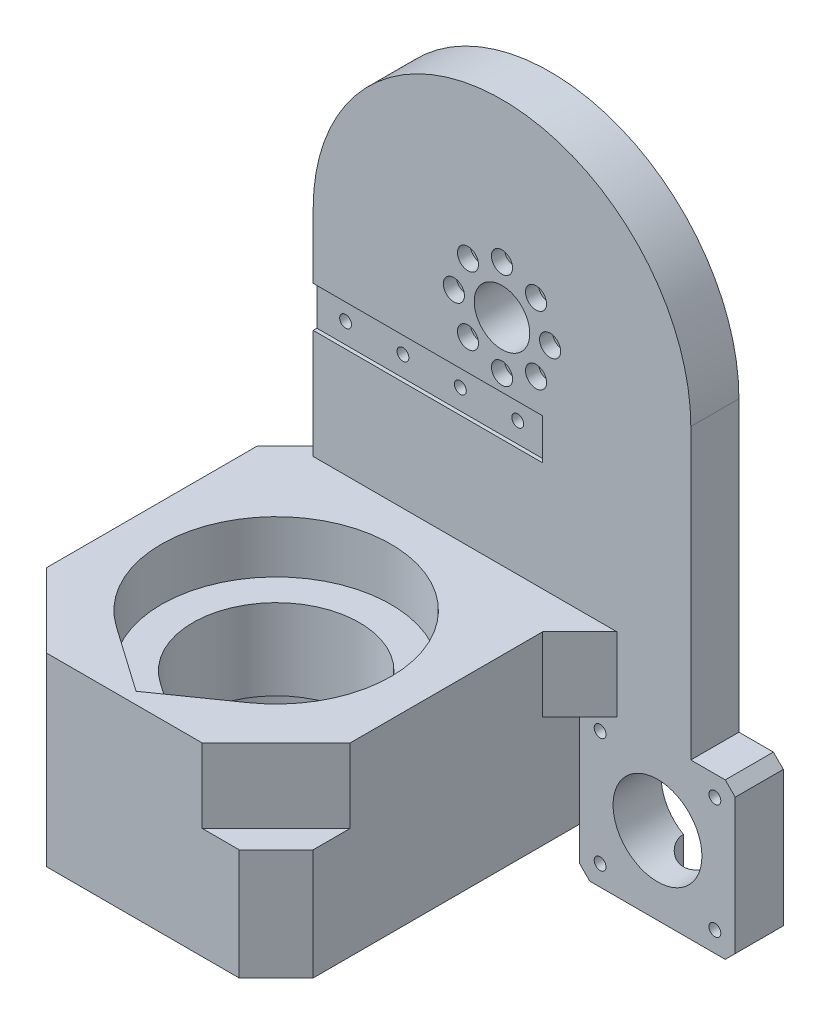
SolidWorks part; units mm, degrees
ref_plane "Front Plane" through (0, 0, 0) normal (1, 0, 0) x (0, 1, 0)
ref_plane "Top Plane" through (0, 0, 0) normal (0, 0, 1) x (0, 1, 0)
ref_plane "Right Plane" through (0, 0, 0) normal (0, 1, 0) x (-1, 0, 0)
sketch "Sketch1" plane through (0, 0, 0) normal (0, 0, 1) x (0, 1, 0)
  line L0 (0, 0) -> (-50000, 0) construction
  line L1 (22, 21) -> (67, 21) construction
  line L2 (22, 21) -> (22, -21) construction
  line L3 (22, -21) -> (67, -21) construction
  line L4 (67, 21) -> (67, -21) construction
  line L5 (-32, 31) -> (-18, 31)
  line L6 (-32, 31) -> (-32, -31)
  line L7 (-32, -31) -> (-18, -31)
  line L8 (-18, 31) -> (-18, -31)
  line L9 (-68, -31) -> (-54, -31)
  line L10 (-54, 31) -> (-54, -31)
  line L11 (-68, 31) -> (-54, 31)
  line L12 (-68, 31) -> (-68, -31)
  line L13 (-80, -43.6985) -> (-77.3015, -41)
  line L14 (-77.3015, -41) -> (-73, -41)
  line L15 (-80, -43.6985) -> (-80, -80.3015)
  line L16 (-77.3015, -83) -> (-40.6985, -83)
  line L17 (-38, -71) -> (-38, -80.3015)
  line L18 (0, 0) -> (0, -20) construction
  line L19 (0, -20) -> (40, -20) construction
  line L22 (40, 41) -> (-68, 41)
  line L24 (-80, -80.3015) -> (-77.3015, -83)
  line L25 (-73, -41) -> (-18, -41)
  line L26 (-18, -41) -> (-18, -31)
  line L27 (-18, 31) -> (-18, 41)
  line L28 (-68, -31) -> (-68, -41)
  line L29 (-68, 41) -> (-68, 31)
  line L30 (40, 41) -> (40, 31)
  line L31 (40, 31) -> (-18, 31)
  line L32 (40, -71) -> (-38, -71)
  line L33 (-40.6985, -83) -> (-38, -80.3015)
  line L34 (-54, 31) -> (-32, 31)
  line L36 (-43.5, -46.5) -> (-74.5, -46.5) construction
  line L37 (-43.5, -46.5) -> (-43.5, -77.5) construction
  line L38 (-43.5, -77.5) -> (-74.5, -77.5) construction
  line L39 (-74.5, -46.5) -> (-74.5, -77.5) construction
  line L40 (-43.5, -46.5) -> (-74.5, -77.5) construction
  line L41 (-43.5, -77.5) -> (-74.5, -46.5) construction
  circle A0 centre (-59, -62) radius 12
  circle A1 centre (40, -20) radius 17.5
  circle A2 centre (40, -20) radius 13 construction
  circle A3 centre (40, -7) radius 1.6
  circle A4 centre (40, -7) radius 2.85
  circle A12 centre (40, -20) radius 7.5
  circle A13 centre (49.1924, -10.8076) radius 2.85
  circle A14 centre (49.1924, -10.8076) radius 1.6
  circle A15 centre (53, -20) radius 2.85
  circle A16 centre (53, -20) radius 1.6
  circle A17 centre (49.1924, -29.1924) radius 2.85
  circle A18 centre (49.1924, -29.1924) radius 1.6
  circle A19 centre (40, -33) radius 2.85
  circle A20 centre (40, -33) radius 1.6
  circle A21 centre (30.8076, -29.1924) radius 2.85
  circle A22 centre (30.8076, -29.1924) radius 1.6
  circle A23 centre (27, -20) radius 2.85
  circle A24 centre (27, -20) radius 1.6
  circle A25 centre (30.8076, -10.8076) radius 2.85
  circle A26 centre (30.8076, -10.8076) radius 1.6
  arc A27 (40, -71) -> (40, 31) centre (40, -20) ccw
  circle A28 centre (-74.5, -46.5) radius 1.6
  circle A29 centre (-74.5, -46.5) radius 2.85
  circle A30 centre (-43.5, -46.5) radius 2.85
  circle A31 centre (-43.5, -46.5) radius 1.6
  circle A32 centre (-43.5, -77.5) radius 2.85
  circle A33 centre (-43.5, -77.5) radius 1.6
  circle A34 centre (-74.5, -77.5) radius 2.85
  circle A35 centre (-74.5, -77.5) radius 1.6
  point P12 (-18, 0)
  point P16 (-54, 0)
  point P17 (22, 0)
  point P18 (-80, -41)
  point P19 (-38, -83)
  point P20 (-80, -83)
  dimension "D13" = 24
  dimension "D14" = 35
  dimension "D15" = 26
  dimension "D16" = 3.2
  dimension "D17" = 5.7
  dimension "D22" = 15
  dimension "D29" = 3.2
  dimension "D30" = 5.7
  dimension "D1" = 42
  dimension "D2" = 45
  dimension "D3" = 22
  dimension "D4" = 14
  dimension "D5" = 62
  dimension "D6" = 40
  dimension "D7" = 62
  dimension "D8" = 14
  dimension "D9" = 22
  dimension "D10" = 31
  dimension "D11" = 60
  dimension "D12" = 10
  dimension "D19" = 20
  dimension "D20" = 10
  dimension "D21" = 40
  dimension "D23" = 59
  dimension "D24" = 31
  dimension "D28" = 21
  dimension "D31" = 2
  dimension "D18" = 8
extrude "Boss-Extrude2" add sketch "Sketch1" against normal blind 13 contours L3 L1 L2 | L34 L10 L9 L28 L25 L26 L7 L6 | L11 L12 L9 L10 | L8 L5 L6 L7 | L32 A27 L31 L8 L26 L25 L14 L13 L15 L24 L16 L33 L17 A0 A1 | A1 A25 A23 A21 A19 A17 A15 A13 A12 A4 | A25 A26 | A4 A3 | A13 A14 | A15 A16 | A17 A18 | A19 A20 | A21 A22 | A23 A24 | A34 A35 | A32 A33 | A30 A31 | A29 A28 region at (0, -25, 0) region at (9.6567, -43, 0) region at (26.6311, 17.6235, 0) region at (0, -61, 0) region at (20, 22.995, 0) region at (7, 37.2306, 0) region at (10.8076, 46.423, 0) region at (20, 50.2306, 0) region at (29.1924, 46.423, 0) region at (33, 37.2306, 0) region at (29.1924, 28.0382, 0) region at (20, 24.2306, 0) region at (10.8076, 28.0382, 0) region at (46.5, -77.2694, 0) region at (46.5, -46.2694, 0) region at (77.5, -46.2694, 0) region at (77.5, -77.2694, 0)
extrude "Boss-Extrude3" add sketch "Sketch1<6>" along normal blind 82 contours L5 L27 L22 L25 L26 L7 L6 L12 L11 L10 L9 | L8 L5 L6 L7 | L11 L12 L9 L10 | L11 L34 L5 L27 L22 L29 region at (-36, -43, 0) region at (0, -25, 0) region at (9.6567, -43, 0) region at (0, -61, 0)
sketch "Sketch1<6>" plane through (0, 0, 0) normal (0, 0, 1) x (0, 1, 0) same geometry as "Sketch1"
extrude "Cut-Extrude2" cut sketch "Sketch1<5>" against normal blind 3.5 contours A21 | A23 | A25 | A4 | A13 | A15 | A17 | A19
sketch "Sketch1<5>" plane through (0, 0, 0) normal (0, 0, 1) x (0, 1, 0) same geometry as "Sketch1"
sketch "Sketch2" plane through (0, -18, 0) normal (0, 1, 0) x (-1, 0, 0)
  line L0 (-41, 82) -> (41, 0) construction
  line L1 (0, 41) -> (0, 78.844) construction
  line L2 (-17.7809, 66.3937) -> (0, 78.844)
  line L3 (17.7809, 66.3937) -> (0, 78.844)
  line L4 (-12.9055, 59.4309) -> (0, 68.4674)
  line L5 (12.9055, 59.4309) -> (0, 68.4674)
  line L6 (31, 0) -> (41, 0) construction
  arc A0 (-17.7809, 66.3937) -> (17.7809, 66.3937) centre (0, 41) ccw
  arc A1 (-12.9055, 59.4309) -> (12.9055, 59.4309) centre (0, 41) ccw
  point P5 (41, 0)
  point P13 (41, 0)
  dimension "D1" = 62
  dimension "D3" = 45
  dimension "D2" = 55
  dimension "D4" = 55
extrude "Cut-Extrude3" cut sketch "Sketch2" against normal blind 14.1 contours A0 L3 L2
extrude "Cut-Extrude4" cut sketch "Sketch2<3>" along normal blind 14.1 from surface starting at face at (-3, -68, 19.7143)
sketch "Sketch2<3>" plane through (0, -18, 0) normal (0, 1, 0) x (-1, 0, 0) same geometry as "Sketch2"
extrude "Cut-Extrude5" cut sketch "Sketch2<4>" against normal through all and the other way through all contours L4 A1 L5 region at (0, -18, 41.6528)
sketch "Sketch2<4>" plane through (0, -18, 0) normal (0, 1, 0) x (-1, 0, 0) same geometry as "Sketch2"
sketch "Sketch3" plane through (0, 0, 0) normal (0, 0, 1) x (1, 0, 0)
  line L1 (21, 22) -> (21, 67) construction
  line L2 (-21, 67) -> (21, 67) construction
  line L3 (-21, 22) -> (-21, 67) construction
  line L4 (-31, -18) -> (-31, 40) construction
  line L5 (21, 22) -> (21, 67) construction
  line L6 (-21, 67) -> (21, 67) construction
  line L7 (-21, 22) -> (-21, 67) construction
  line L8 (-21, 22) -> (21, 22) construction
  line L9 (-21, 22) -> (21, 22) construction
  line L10 (0, 22) -> (0, 17) construction
  line L11 (31, 11.5) -> (-31, 11.5)
  line L12 (31, 11.5) -> (31, 22.5)
  line L13 (31, 22.5) -> (-31, 22.5)
  line L14 (-31, 11.5) -> (-31, 22.5)
  line L15 (31, 11.5) -> (-31, 22.5) construction
  line L16 (31, 22.5) -> (-31, 11.5) construction
  line L17 (-31, 17) -> (-23.25, 17) construction
  circle A0 centre (-23.25, 17) radius 1.6
  circle A1 centre (-23.25, 17) radius 2.85
  circle A2 centre (-7.75, 17) radius 1.6
  circle A3 centre (-7.75, 17) radius 2.85
  circle A4 centre (7.75, 17) radius 1.6
  circle A5 centre (7.75, 17) radius 2.85
  circle A6 centre (23.25, 17) radius 1.6
  circle A7 centre (23.25, 17) radius 2.85
  dimension "D5" = 3.2
  dimension "D6" = 5.7
  dimension "D1" = 5
  dimension "D2" = 11
  dimension "D3" = 62
  dimension "D4" = 7.75
  dimension "D7" = 4
extrude "Cut-Extrude6" cut sketch "Sketch3" against normal blind 1 contours L13 L14 L11 L12
extrude "Cut-Extrude7" cut sketch "Sketch3<3>" against normal through all contours A0 | A2 | A4 | A6
sketch "Sketch3<3>" plane through (0, 0, 0) normal (0, 0, 1) x (1, 0, 0) same geometry as "Sketch3"
extrude "Cut-Extrude8" cut sketch "Sketch3<5>" along normal blind 3.5 from surface contours A1 | A3 | A5 | A7 starting at face at (-21.65, 17, -13)
sketch "Sketch3<5>" plane through (0, 0, 0) normal (0, 0, 1) x (1, 0, 0) same geometry as "Sketch3"
extrude "Cut-Extrude9" cut sketch "Sketch1<7>" along normal blind 3.5 from surface contours A29 | A34 | A32 | A30 starting at face at (-20.4, 17, -13)
sketch "Sketch1<7>" plane through (0, 0, 0) normal (0, 0, 1) x (0, 1, 0) same geometry as "Sketch1"
sketch "Sketch4" plane through (0, -80, 0) normal (0, -1, 0) x (1, 0, 0)
  line L0 (62, -13) -> (62, -7) construction
  line L1 (43.6985, -13) -> (80.3015, -13) construction
  line L2 (56, -13) -> (68, -13)
  arc A0 (56, -13) -> (68, -13) centre (62, -13) cw
  point P7 (62, -7)
  dimension "D1" = 6
extrude "Cut-Extrude10" cut sketch "Sketch4" against normal blind 12.5 contours A0 L2
sketch "Sketch5" plane through (0, -18, 0) normal (0, 1, 0) x (-1, 0, 0)
  line L0 (-41, 0) -> (-51, 0)
  line L2 (-41, 10) -> (-41, 0)
  line L3 (31, 0) -> (41, 0)
  line L4 (41, 5) -> (41, 0)
  line L5 (31, 0) -> (-71, 0) construction
  line L6 (-51, 0) -> (-41, 10)
  line L7 (-41, 62) -> (-21, 82)
  line L8 (21, 82) -> (41, 62)
  line L9 (-41, 62) -> (-41, 82)
  line L10 (-41, 82) -> (-21, 82)
  line L11 (21, 82) -> (41, 82)
  line L12 (41, 82) -> (41, 62)
  line L13 (41, 5) -> (31, -5)
  line L14 (31, -13) -> (31, 0) construction
  line L15 (31, -5) -> (31, 0)
  point P0 (-41, 82)
  point P3 (41, 82)
  line M6 (31, 0) -> (41, 0)
  line M7 (41, 0) -> (41, 82)
  line M8 (41, 82) -> (-41, 82)
  dimension "D1" = 10
  dimension "D2" = 45
  dimension "D3" = 5
  dimension "D4" = 45
extrude "Boss-Extrude4" add sketch "Sketch5" against normal up to surface (50 mm away) contours L15 L13 M6 region at (-32.6667, -18, -1.6667) up to face at (0, -68, 51.7459)
extrude "Cut-Extrude11" cut sketch "Sketch5<3>" against normal blind 50.5 contours L8 M8 M7 | L13 L3 M7 region at (-34.3333, -18, 75.3333) region at (-39.3333, -18, 1.6667)
sketch "Sketch5<3>" plane through (0, -18, 0) normal (0, 1, 0) x (-1, 0, 0) same geometry as "Sketch5"
extrude "Boss-Extrude5" add sketch "Sketch5<4>" against normal up to surface (20 mm away) contours L6 L0 L2 region at (44.3333, -18, 3.3333) up to face at (75.6508, -38, -6.5)
sketch "Sketch5<4>" plane through (0, -18, 0) normal (0, 1, 0) x (-1, 0, 0) same geometry as "Sketch5"
extrude "Cut-Extrude12" cut sketch "Sketch5<5>" against normal up to surface (20 mm away) contours L7 L10 L9 up to face at (75.6508, -38, -6.5)
sketch "Sketch5<5>" plane through (0, -18, 0) normal (0, 1, 0) x (-1, 0, 0) same geometry as "Sketch5"
chamfer "Chamfer6" distance 10 angle 45 1 edges at (41, -53, 82)
